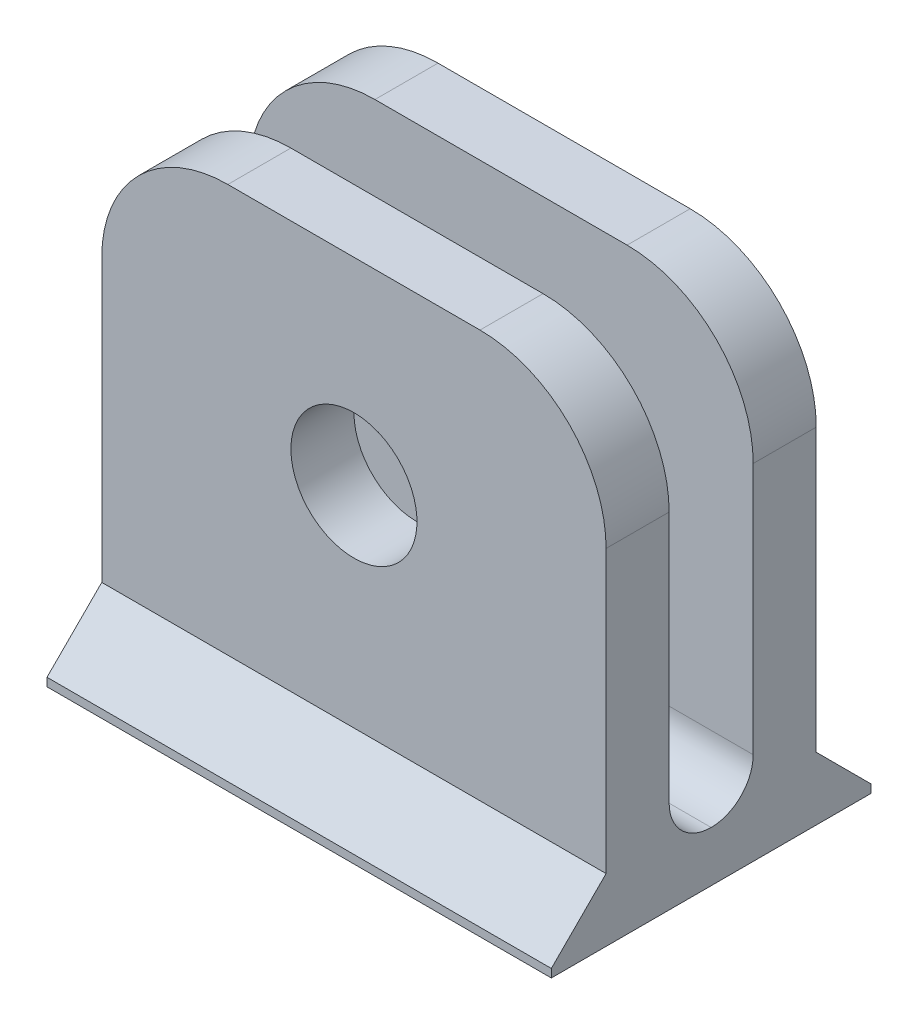
SolidWorks part; units mm, degrees
ref_plane "Front Plane" through (0, 0, 0) normal (0, 0, 1) x (1, 0, 0)
ref_plane "Top Plane" through (0, 0, 0) normal (0, 1, 0) x (1, 0, 0)
ref_plane "Right Plane" through (0, 0, 0) normal (1, 0, 0) x (0, 0, -1)
sketch "Sketch1" plane through (0, 0, 0) normal (0, 1, 0) x (1, 0, 0)
  line L1 (0, 0) -> (12, 0)
  line L2 (0, 0) -> (0, -5)
  line L3 (0, -5) -> (12, -5)
  line L4 (12, 0) -> (12, -5)
  dimension "D1" = 5
  dimension "D2" = 12
extrude "Boss-Extrude1" add sketch "Sketch1" along normal blind 1.2
sketch "Sketch2" plane through (0, 1.2, 0) normal (0, 1, 0) x (1, 0, 0)
  line L0 (12, -5) -> (12, 0) construction
  line L1 (0, -5) -> (12, -5)
  line L2 (0, -5) -> (0, -3.5)
  line L3 (0, -3.5) -> (12, -3.5)
  line L4 (12, -5) -> (12, -3.5)
  line L5 (0, 0) -> (0, -5) construction
  line L6 (12, 0) -> (0, 0)
  line L7 (12, 0) -> (12, -1.5)
  line L8 (12, -1.5) -> (0, -1.5)
  line L9 (0, 0) -> (0, -1.5)
  dimension "D1" = 1.5
  dimension "D2" = 1.5
extrude "Boss-Extrude2" add sketch "Sketch2" along normal blind 10
fillet "Fillet1" radius 3 4 edges at (12, 11.2, 0.75) (0, 11.2, 0.75) (0, 11.2, 4.25) (12, 11.2, 4.25)
fillet "Fillet2" radius 1 2 edges at (6, 1.2, 3.5) (6, 1.2, 1.5)
sketch "Sketch3" plane through (0, 0, 0) normal (0, 0, -1) x (-1, 0, 0)
  line L0 (-12, 0) -> (0, 0) construction
  line L1 (-12, 8.2) -> (-12, 0) construction
  circle A0 centre (-6, 6.5) radius 1.5
  dimension "D1" = 3
  dimension "D2" = 6.5
  dimension "D3" = 6
extrude "Cut-Extrude1" cut sketch "Sketch3" against normal through all
sketch "Sketch4" plane through (12, 0, 0) normal (1, 0, 0) x (0, 0, -1)
  line L0 (0, 1.5) -> (1.3031, 0.1969)
  line L1 (0, 8.2) -> (0, 0) construction
  line L2 (1.3031, 0) -> (0, 0)
  line L3 (0, 0) -> (0, 1.5)
  line L4 (-2.5, 0) -> (-2.5, 2.952) construction
  line L5 (-5, 0) -> (0, 0) construction
  line L6 (-6.3031, 0) -> (-6.3031, 0.1969)
  line L7 (-5, 1.5) -> (-6.3031, 0.1969)
  line L8 (-5, 0) -> (-5, 1.5)
  line L9 (1.3031, 0) -> (1.3031, 0.1969)
  line L10 (-6.3031, 0) -> (-5, 0)
  point P15 (2.1086, -1.8183)
  dimension "D1" = 1.3031
  dimension "D2" = 1.5
  dimension "D3" = 1.8428
extrude "Boss-Extrude3" add sketch "Sketch4" against normal blind 12
